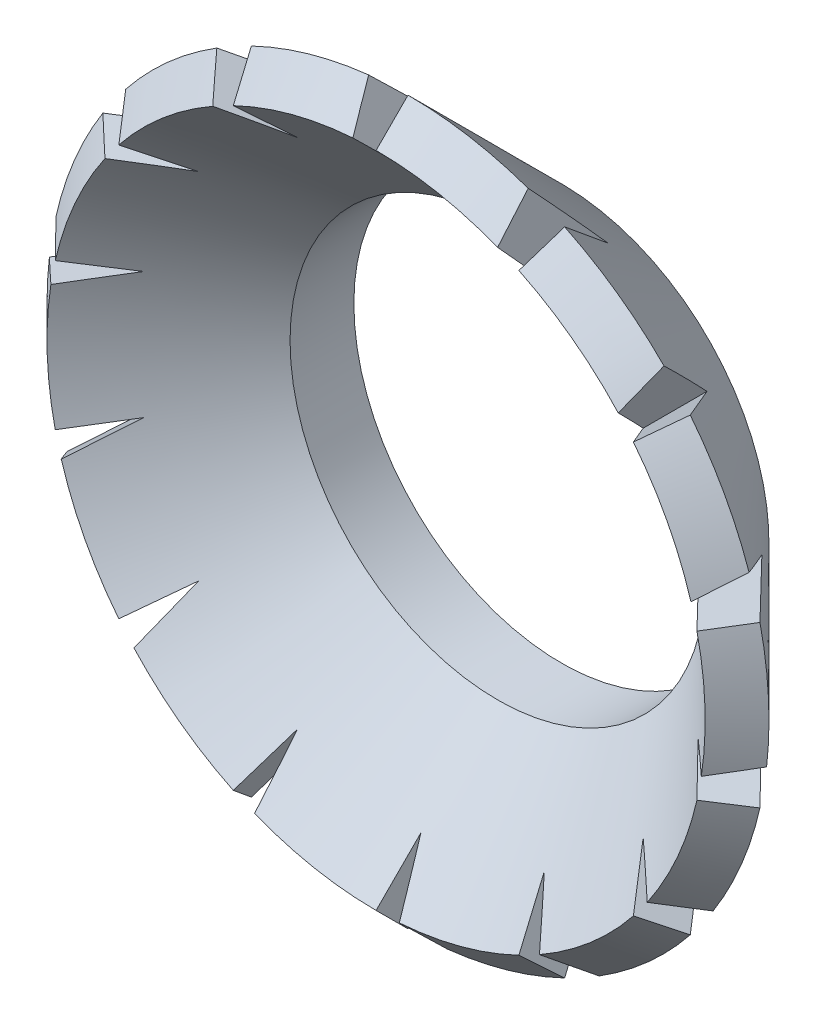
SolidWorks part; units mm, degrees
ref_plane "Front" through (0, 0, 0) normal (0, 0, 1) x (1, 0, 0)
ref_plane "Top" through (0, 0, 0) normal (0, 1, 0) x (1, 0, 0)
ref_plane "Right" through (0, 0, 0) normal (1, 0, 0) x (0, 0, -1)
sketch "Sketch1" plane through (0, 0, 0) normal (0, 1, 0) x (1, 0, 0)
  line L0 (2.3, 0) -> (4, -1.7)
  line L1 (-50, 0) -> (50, 0) construction
  line L2 (4, -1.7) -> (0, -1.7) construction
  line L3 (0, -50) -> (0, 50) construction
  line L4 (2.3, 0) -> (0, 2.3) construction
  line L5 (2.3, 0) -> (2.3, -0.7071)
  line L6 (2.3, -0.7071) -> (3.6464, -2.0536)
  line L7 (3.6464, -2.0536) -> (4, -1.7)
  line L8 (0, 3.758) -> (0, -5.7704) construction
  dimension "D1" = 45
  dimension "S" = 0.5
sketch "Sketch2" plane through (0, 0, 0) normal (0, 0, 1) x (1, 0, 0)
  line L0 (0, 0) -> (14, 0) construction
  line L1 (0, 4) -> (-0.4488, 4)
  line L2 (-0.4488, 4) -> (0, 3.15)
  line L3 (0, 3.15) -> (0, 4)
  circle A0 centre (0, 0) radius 3.15 construction
  circle A1 centre (0, 0) radius 4 construction
  dimension "D1" = 6.3
  dimension "D4" = 8
  dimension "D2" = 0.4488
revolve "Revolve1" add sketch "Sketch1" angle 360 about L8
extrude "Cut-Extrude1" cut sketch "Sketch2" along normal through all
ref_axis "Axis1" through (0, 0, -9.0154) along (0, 0, 1)
pattern_circular "TypeApatten" count 14 over 360 about axis through (0, 0, -9.0154) along (0, 0, 1) of "Cut-Extrude1"
equation "\"D4@Sketch2\"=\"D0@Sketch1\""
equation "\"D1@Sketch2\" =  ( \"D0@Sketch1\" + \"d@Sketch1\" )  / 2"
equation "\"D2@Sketch2\" = \"D4@Sketch2\" *  pi  / \"D3@Sketch2\"  / 4"
equation "\"D1@TypeApatten\" = \"D3@Sketch2\""
